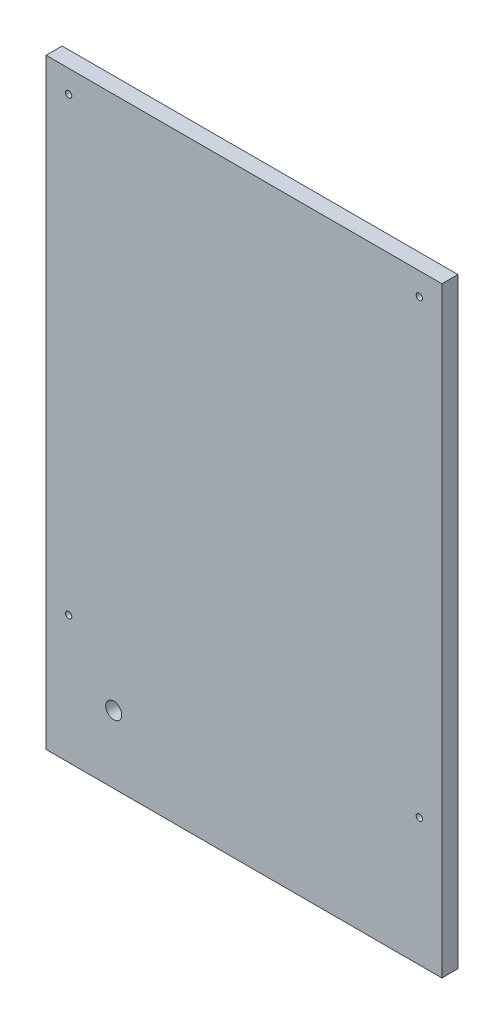
SolidWorks part; units mm, degrees
ref_plane "Front Plane" through (0, 0, 0) normal (0, 0, 1) x (1, 0, 0)
ref_plane "Top Plane" through (0, 0, 0) normal (0, 1, 0) x (1, 0, 0)
ref_plane "Right Plane" through (0, 0, 0) normal (1, 0, 0) x (0, 0, -1)
sketch "Sketch1" plane through (0, 0, 0) normal (0, 0, 1) x (1, 0, 0)
  line L1 (0, 0) -> (395, 0)
  line L2 (0, 0) -> (0, 600)
  line L3 (0, 600) -> (395, 600)
  line L4 (395, 0) -> (395, 600)
  dimension "D1" = 600
  dimension "D2" = 395
extrude "Base" add sketch "Sketch1" along normal blind 16
sketch "Sketch2" plane through (0, 0, 16) normal (0, 0, 1) x (1, 0, 0)
  line L0 (197.5, 600) -> (197.5, 0) construction
  line L1 (22.5, 577.5) -> (0, 577.5) construction
  line L2 (0, 600) -> (0, 0) construction
  line L3 (395, 600) -> (0, 600) construction
  line L4 (22.5, 577.5) -> (22.5, 600) construction
  line L5 (22.5, 600) -> (22.5, 0) construction
  line L6 (0, 0) -> (395, 0) construction
  line L8 (395, 300) -> (0, 300) construction
  line L9 (395, 0) -> (395, 600) construction
  line L10 (0, 600) -> (0, 0) construction
  circle A0 centre (22.5, 577.5) radius 3.15
  circle A1 centre (372.5, 577.5) radius 3.15
  circle A2 centre (22.5, 127.5) radius 3.15
  circle A3 centre (372.5, 127.5) radius 3.15
  dimension "D1" = 6.3
  dimension "D2" = 350
  dimension "D3" = 450
extrude "Mounting holes" cut sketch "Sketch2" against normal through all
sketch "Sketch3" [suppressed] plane through (0, 0, 0) normal (0, 0, -1) x (-1, 0, 0)
  line L0 (-395, 600) -> (0, 0) construction
  line L1 (-395, 0) -> (0, 600) construction
  line L2 (-395, 0) -> (-395, 600) construction
  line L3 (-356.5, 38.5) -> (-38.5, 38.5)
  line L4 (-356.5, 38.5) -> (-356.5, 561.5)
  line L5 (-356.5, 561.5) -> (-38.5, 561.5)
  line L6 (-38.5, 38.5) -> (-38.5, 561.5)
  line L7 (-356.5, 38.5) -> (-38.5, 561.5) construction
  line L8 (-356.5, 561.5) -> (-38.5, 38.5) construction
  line L9 (-356.5, 300) -> (-395, 300) construction
  line L10 (-197.5, 561.5) -> (-197.5, 600) construction
  line L11 (-395, 600) -> (0, 600) construction
  line L12 (-57.75, 38.5) -> (-57.75, 77) construction
  line L13 (-38.5, 38.5) -> (-356.5, 38.5)
  line L14 (-38.5, 38.5) -> (-38.5, 77)
  line L15 (-38.5, 77) -> (-356.5, 77)
  line L16 (-356.5, 38.5) -> (-356.5, 77)
  line L17 (-77, 57.75) -> (-38.5, 57.75) construction
  line L18 (-38.5, 38.5) -> (-77, 38.5)
  line L19 (-38.5, 38.5) -> (-38.5, 77)
  line L20 (-38.5, 77) -> (-77, 77)
  line L21 (-77, 38.5) -> (-77, 77)
  point P8 (-197.5, 300)
  point P29 (-57.75, 57.75)
  dimension "D1" = 38.5
extrude "Center hole" [suppressed] cut sketch "Sketch3" against normal up to next contours L15 L6 L5 L4 | L21 L13 L6 L15
sketch "Sketch4" plane through (0, 0, 0) normal (0, 0, -1) x (-1, 0, 0)
  line L0 (0, 0) -> (-395, 0) construction
  line L1 (0, 600) -> (-45, 600)
  line L2 (-395, 0) -> (-395, 600) construction
  line L3 (0, 600) -> (0, 0)
  line L4 (0, 0) -> (-395, 0)
  line L5 (0, 0) -> (0, 45)
  line L6 (0, 0) -> (-45, 0)
  line L7 (0, 45) -> (-395, 45)
  line L8 (-395, 0) -> (-395, 45)
  line L9 (-45, 600) -> (-45, 0)
  line L10 (-22.5, 0) -> (-22.5, 600) construction
  line L11 (-22.5, 577.5) -> (0, 577.5) construction
  line L12 (-197.5, 0) -> (-197.5, 45) construction
  line L14 (-67.5, 90) -> (-67.5, 45) construction
  line L15 (-45, 45) -> (-90, 45)
  line L16 (-45, 45) -> (-45, 90)
  line L17 (-45, 90) -> (-90, 90)
  line L18 (-90, 45) -> (-90, 90)
  line L19 (-90, 67.5) -> (-45, 67.5) construction
  line L20 (-45, 300) -> (0, 300) construction
  circle A0 centre (-67.5, 67.5) radius 8
  dimension "D1" = 16
extrude "Tap hole" cut sketch "Sketch4" against normal up to next contours A0
equation "\"D2@Sketch2\"=\"GridSize\"*7"
equation "\"D1@Sketch3\"=2*19.25"
equation "\"GridSize\"= 50"
equation "\"D3@Sketch2\"=\"GridSize\"*9"
equation "\"TapHoleSize\"=16"
equation "\"D1@Sketch4\"=\"TapHoleSize\""
